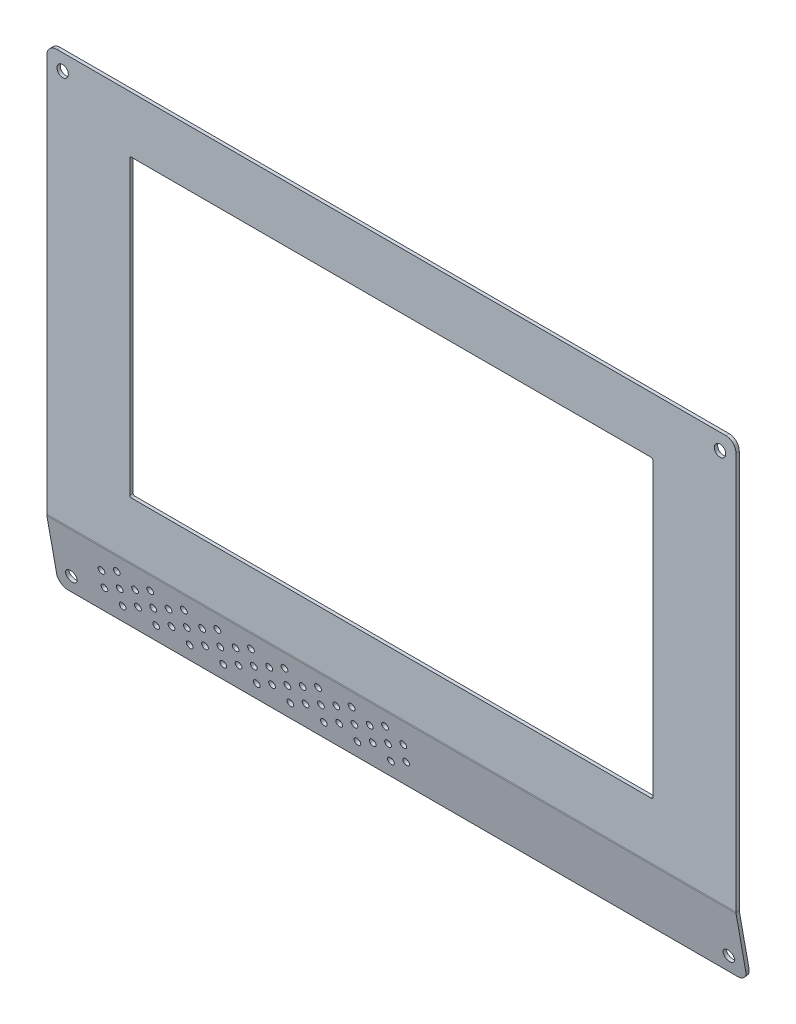
SolidWorks part; units mm, degrees
note: The reader was unsure of these and kept them because the rebuilt part matched: flange length of "Ребро-кромка1".
ref_plane "Спереди" through (0, 0, 0) normal (0, 0, 1) x (1, 0, 0)
ref_plane "Сверху" through (0, 0, 0) normal (0, 1, 0) x (1, 0, 0)
ref_plane "Справа" through (0, 0, 0) normal (1, 0, 0) x (0, 0, -1)
sketch "Эскиз2" plane through (0, 0, 0) normal (0, 0, 1) x (1, 0, 0)
  line L1 (102.75, 60.75) -> (-102.75, 60.75)
  line L2 (102.75, 60.75) -> (102.75, -60.75)
  line L3 (102.75, -60.75) -> (-102.75, -60.75)
  line L4 (-102.75, 60.75) -> (-102.75, -60.75)
  line L5 (102.75, 60.75) -> (-102.75, -60.75) construction
  line L6 (102.75, -60.75) -> (-102.75, 60.75) construction
  point P0 (0, 0)
  dimension "D1" = 205.5
  dimension "D2" = 121.5
base flange "Базовая кромка1" sketch "Эскиз2" thickness 1 reverse thickness direction no parameters "D1"=1.6
edge flange "Ребро-кромка1" sketch "Эскиз11" flange angle 170 flange length 20 flange position bend outside bend radius 1.6 thickness 1 relief rectangular parameters "D6"=10
sketch "Эскиз11" plane through (0, -60.75, -1) normal (0, -0.1736, 0.9848) x (-1, 0, 0)
  line L0 (102.75, 0) -> (-102.75, 0) construction
  line L1 (102.75, 0) -> (-102.75, 0)
  line L2 (-102.75, 0) -> (-102.75, 19.9125)
  line L3 (-102.75, 19.9125) -> (102.75, 19.9125)
  line L4 (102.75, 19.9125) -> (102.75, 0)
bend "EdgeBend1" bend radius 1.6 bend angle 10 parameters "D5"=1
fillet "Скругление1" radius 3 4 edges at (102.75, -80.5868, -3.9654) (-102.75, -80.5868, -3.9654) (-102.75, 60.75, -0.5) (102.75, 60.75, -0.5)
sketch "Эскиз12" plane through (0, 0, 0) normal (0, 0, 1) x (1, 0, 0)
  line L1 (78, -44) -> (-78, -44)
  line L2 (78, -44) -> (78, 44)
  line L3 (78, 44) -> (-78, 44)
  line L4 (-78, -44) -> (-78, 44)
  line L5 (78, -44) -> (-78, 44) construction
  line L6 (78, 44) -> (-78, -44) construction
  point P0 (0, 0)
  dimension "D1" = 156
  dimension "D2" = 88
extrude "Вырез-Вытянуть2" cut sketch "Эскиз12" against normal blind 10 normal cut yes
fillet "Скругление2" radius 0.5 4 edges at (78, -44, -0.5) (78, 44, -0.5) (-78, 44, -0.5) (-78, -44, -0.5)
hole_wizard "Сверло под метчик  спиральное M31" positions "Трехмерный эскиз3" profile "Эскиз15" hole size "M3" standard "Ansi Metric"
sketch3d "Трехмерный эскиз3"
  circle A0 centre (-98.0213, -75.5969, -3.5932) radius 1.575 construction
  circle A1 centre (98.0213, -75.5969, -3.5932) radius 1.575 construction
  circle A2 centre (98.0213, 55.9949, -1.0022) radius 1.575 construction
  circle A3 centre (-98.0213, 55.9949, -1.0022) radius 1.575 construction
  point P3 (-98.0213, -75.7706, -2.6084)
  point P10 (-98.0213, -75.8704, -2.0422)
  point P17 (98.0213, -75.7706, -2.6084)
  point P26 (98.0213, -75.8704, -2.0422)
  point P27 (-98.0213, 55.9949, 0)
  point P29 (98.0213, 55.9949, 0)
  point P35 (98.0213, 55.9949, 0.5728)
  point P39 (-98.0213, 55.9949, 0.5728)
sketch "Эскиз15" plane through (-98.0213, -75.7706, -2.6084) normal (1, 0, 0) x (0, -0.9848, -0.1736)
  line L0 (0, 0) -> (0, 9.5215)
  line L1 (0, 9.5215) -> (1.7, 8.5)
  line L2 (1.7, 8.5) -> (1.7, 0)
  line L5 (1.7, 0) -> (0, 0)
  line L10 (0, 9.5215) -> (-1.7, 8.5) construction
  line L11 (0, -6.35) -> (0, 107.95) construction
  dimension "Диаметр отверстия" = 3.4
  dimension "Глубина отверстия" = 8.5
  dimension "Угол заточки сверла" = 118
sketch "Эскиз16" plane through (0, -1.8387, 10.4278) normal (0, -0.1736, 0.9848) x (1, 0, 0)
  line L0 (-42.75, -80.0511) -> (-42.75, -60.2786) construction
  line L3 (-102.75, -70.1648) -> (102.75, -70.1648) construction
  line L4 (-102.75, -60.2786) -> (-102.75, -77.0511) construction
  line L5 (102.75, -77.0511) -> (102.75, -60.2786) construction
  circle A0 centre (-42.75, -70.1648) radius 1
  circle A1 centre (-42.75, -65.1648) radius 1
  circle A2 centre (-42.75, -75.1648) radius 1
  dimension "D1" = 2
  dimension "D2" = 5
  dimension "D3" = 5
  dimension "D4" = 60
extrude "Вырез-Вытянуть3" cut sketch "Эскиз16" against normal blind 10
pattern_linear "Линейный массив1" count 5 spacing 10 along (1, 0, 0) count 5 spacing 10 along (-1, 0, 0) of "Вырез-Вытянуть3" pattern seed only yes
sketch "Эскиз17" plane through (0, -1.8387, 10.4278) normal (0, -0.1736, 0.9848) x (1, 0, 0)
  line L0 (-52.75, -70.1648) -> (-42.75, -75.1648) construction
  line L1 (-42.75, -70.1648) -> (-52.75, -75.1648) construction
  line L2 (-52.75, -65.1648) -> (-42.75, -70.1648) construction
  line L3 (-52.75, -70.1648) -> (-42.75, -65.1648) construction
  circle A0 centre (-47.75, -67.6648) radius 1
  circle A1 centre (-47.75, -72.6648) radius 1
  circle A2 centre (-42.75, -75.1648) radius 1 construction
extrude "Вырез-Вытянуть4" cut sketch "Эскиз17" against normal blind 1 normal cut yes
pattern_linear "Линейный массив2" count 6 spacing 10 along (1, 0, 0) count 5 spacing 10 along (-1, 0, 0) of "Вырез-Вытянуть4" pattern seed only yes
sketch "Сгиб-Линии1" plane through (0, 0, 0) normal (0, 1, 0) x (1, 0, 0)
sketch "Граничная рамка1" plane through (0, 0, 0) normal (0, 1, 0) x (1, 0, 0)
sheet metal parameters "Листовой металл6" thickness 1 parameters "D1"=1.6
flat pattern "Развертка6" [suppressed]
sketch "Сгиб-Линии2" plane through (0, 0, 0) normal (0, 1, 0) x (1, 0, 0)
sketch "Граничная рамка2" [suppressed] plane through (0, 0, 0) normal (0, 1, 0) x (1, 0, 0)
sheet metal parameters "Листовой металл7" thickness 1 parameters "D1"=1.6
flat pattern "Развертка6" [suppressed]
sketch "Сгиб-Линии2" plane through (0, 0, 0) normal (0, 1, 0) x (1, 0, 0)
sketch "Граничная рамка2" [suppressed] plane through (0, 0, 0) normal (0, 1, 0) x (1, 0, 0)
bend of the flat pattern "Плоское состояние-<EdgeBend1>1"
sheet metal parameters "Листовой металл8" thickness 1 parameters "D1"=1.6
flat pattern "Развертка6" [suppressed]
sketch "Сгиб-Линии2" plane through (0, 0, 0) normal (0, 1, 0) x (1, 0, 0)
sketch "Граничная рамка2" [suppressed] plane through (0, 0, 0) normal (0, 1, 0) x (1, 0, 0)
bend of the flat pattern "Плоское состояние-<EdgeBend1>1"
sheet metal parameters "Листовой металл9" thickness 1 parameters "D1"=1.6
flat pattern "Развертка6" [suppressed]
sketch "Сгиб-Линии2" plane through (0, 0, 0) normal (0, 1, 0) x (1, 0, 0)
sketch "Граничная рамка2" [suppressed] plane through (0, 0, 0) normal (0, 1, 0) x (1, 0, 0)
bend of the flat pattern "Плоское состояние-<EdgeBend1>1"
sheet metal parameters "Листовой металл11" thickness 1 parameters "D1"=1.6
flat pattern "Развертка6" [suppressed]
sketch "Сгиб-Линии2" plane through (0, 0, 0) normal (0, 1, 0) x (1, 0, 0)
sketch "Граничная рамка2" [suppressed] plane through (0, 0, 0) normal (0, 1, 0) x (1, 0, 0)
bend of the flat pattern "Плоское состояние-<EdgeBend1>1"
sheet metal parameters "Листовой металл12" thickness 1 parameters "D1"=1.6
flat pattern "Развертка6" [suppressed]
sketch "Сгиб-Линии2" plane through (0, 0, 0) normal (0, 1, 0) x (1, 0, 0)
sketch "Граничная рамка2" [suppressed] plane through (0, 0, 0) normal (0, 1, 0) x (1, 0, 0)
bend of the flat pattern "Плоское состояние-<EdgeBend1>1"
sheet metal parameters "Листовой металл13" thickness 1 parameters "D1"=1.6
flat pattern "Развертка6" [suppressed]
sketch "Сгиб-Линии2" plane through (0, 0, 0) normal (0, 1, 0) x (1, 0, 0)
sketch "Граничная рамка2" [suppressed] plane through (0, 0, 0) normal (0, 1, 0) x (1, 0, 0)
bend of the flat pattern "Плоское состояние-<EdgeBend1>1"
sheet metal parameters "Листовой металл14" thickness 1 parameters "D1"=1.6
flat pattern "Развертка6" [suppressed]
sketch "Сгиб-Линии2" plane through (0, 0, 0) normal (0, 1, 0) x (1, 0, 0)
sketch "Граничная рамка2" [suppressed] plane through (0, 0, 0) normal (0, 1, 0) x (1, 0, 0)
bend of the flat pattern "Плоское состояние-<EdgeBend1>1"
